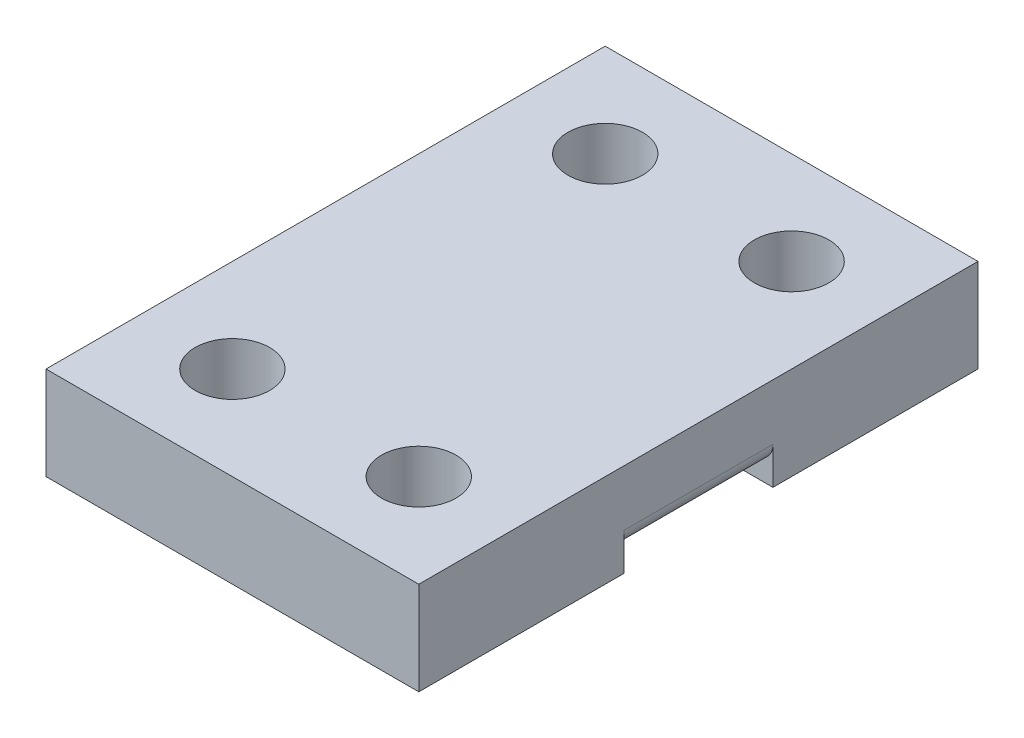
SolidWorks part; units mm, degrees
ref_plane "정면" through (0, 0, 0) normal (0, 0, 1) x (1, 0, 0)
ref_plane "윗면" through (0, 0, 0) normal (0, 1, 0) x (1, 0, 0)
ref_plane "우측면" through (0, 0, 0) normal (1, 0, 0) x (0, 0, -1)
sketch "스케치1" plane through (0, 0, 0) normal (0, 1, 0) x (1, 0, 0)
  line L0 (0, 0) -> (0, 30) construction
  line L1 (-10, 30) -> (10, 30)
  line L2 (10, 30) -> (10, 0)
  line L3 (-10, 30) -> (-10, 0)
  line L4 (10, 0) -> (-10, 0)
  line L5 (5, 25) -> (-5, 25) construction
  line L6 (5, 25) -> (5, 5) construction
  line L7 (-5, 25) -> (-5, 5) construction
  line L8 (5, 5) -> (-5, 5) construction
  circle A0 centre (5, 25) radius 2
  circle A1 centre (-5, 25) radius 2
  circle A2 centre (5, 5) radius 2
  circle A3 centre (-5, 5) radius 2
  point P16 (0, 25)
  point P17 (0, 5)
  dimension "D3" = 4
  dimension "D1" = 30
  dimension "D2" = 20
  dimension "D4" = 5
  dimension "D5" = 10
  dimension "D6" = 20
extrude "보스-돌출1" add sketch "스케치1" along normal blind 5
sketch "스케치3" plane through (0, 0, -30) normal (0, 0, -1) x (-1, 0, 0)
  line L0 (0, 0) -> (-1, 1)
  line L1 (-10, 0) -> (10, 0) construction
  line L2 (-1, 1) -> (-1, 0)
  line L3 (-1, 0) -> (0, 0)
  line L4 (0, 0) -> (1, 1)
  line L5 (1, 1) -> (1, 0)
  line L6 (1, 0) -> (0, 0)
  line L7 (1, 0) -> (2, 0)
  line L8 (2, 0) -> (1, 1)
  line L9 (1, 1) -> (1, 0)
  line L10 (2, 0) -> (3, 1)
  line L11 (3, 1) -> (3, 0)
  line L12 (3, 0) -> (2, 0)
  line L13 (3, 0) -> (4, 0)
  line L14 (4, 0) -> (3, 1)
  line L15 (3, 1) -> (3, 0)
  line L16 (4, 0) -> (5, 1)
  line L17 (5, 1) -> (5, 0)
  line L18 (5, 0) -> (4, 0)
  line L19 (5, 0) -> (6, 0)
  line L20 (6, 0) -> (5, 1)
  line L21 (5, 1) -> (5, 0)
  line L22 (6, 0) -> (7, 1)
  line L23 (7, 1) -> (7, 0)
  line L24 (7, 0) -> (6, 0)
  line L25 (7, 0) -> (8, 0)
  line L26 (8, 0) -> (7, 1)
  line L27 (7, 1) -> (7, 0)
  line L28 (8, 0) -> (9, 1)
  line L29 (9, 1) -> (9, 0)
  line L30 (9, 0) -> (8, 0)
  line L31 (9, 0) -> (10, 0)
  line L32 (10, 0) -> (9, 1)
  line L33 (9, 1) -> (9, 0)
  line L37 (0, 0) -> (0, 5) construction
  line L38 (-10, 5) -> (10, 5) construction
  line L39 (-9, 0) -> (-10, 0)
  line L40 (-10, 0) -> (-9, 1)
  line L41 (-9, 1) -> (-9, 0)
  line L42 (-9, 0) -> (-8, 0)
  line L43 (-9, 1) -> (-9, 0)
  line L44 (-8, 0) -> (-9, 1)
  line L45 (-7, 1) -> (-7, 0)
  line L46 (-8, 0) -> (-7, 1)
  line L47 (-7, 0) -> (-8, 0)
  line L48 (-7, 0) -> (-6, 0)
  line L49 (-7, 1) -> (-7, 0)
  line L50 (-6, 0) -> (-7, 1)
  line L51 (-5, 1) -> (-5, 0)
  line L52 (-6, 0) -> (-5, 1)
  line L53 (-5, 0) -> (-6, 0)
  line L54 (-5, 0) -> (-4, 0)
  line L55 (-5, 1) -> (-5, 0)
  line L56 (-4, 0) -> (-5, 1)
  line L57 (-3, 1) -> (-3, 0)
  line L58 (-4, 0) -> (-3, 1)
  line L59 (-3, 0) -> (-4, 0)
  line L60 (-3, 0) -> (-2, 0)
  line L61 (-3, 1) -> (-3, 0)
  line L62 (-2, 0) -> (-3, 1)
  line L63 (10, 0) -> (11, 1) [skipped]
  line L64 (11, 1) -> (11, 0) [skipped]
  line L65 (11, 0) -> (10, 0) [skipped]
  line L66 (-1, 1) -> (-2, 0)
  line L67 (-9, 1) -> (-10, 1)
  line L68 (-10, 5) -> (-10, 0) construction
  line L69 (-10, 1) -> (-10, 0)
  line L70 (9, 1) -> (10, 1)
  line L71 (10, 5) -> (10, 0) construction
  line L72 (10, 1) -> (10, 0)
  line M7 (-10, 0) -> (10, 0)
  line M8 (10, 0) -> (10, 5)
  line M10 (-10, 5) -> (-10, 0)
  dimension "D1" = 2
  dimension "D2" = 1
  dimension "D3" = 6
extrude "컷-돌출6" cut sketch "스케치3" against normal blind 4 and the other way blind 4 from offset 15 contours L41 L40 M7 | L44 L41 M7 | L46 L45 M7 | L50 L45 M7 | L52 L51 M7 | L56 L51 M7 | L58 L57 M7 | L62 L57 M7 | L2 L66 M7 | L0 L2 M7 | L5 L4 M7 | L8 L5 M7 | L11 L10 M7 | L14 L11 M7 | L20 L17 M7 | L23 L22 M7 | L26 L23 M7 | L29 L28 M7 | L32 L29 M7 | L40 L67 M10 | L70 L32 M8 | L16 L17 L18 region at (0.6667, 0.3333, -30) region at (8.6667, 0.3333, -30) region at (6.6667, 0.3333, -30) region at (4.6667, 0.3333, -30) region at (2.6667, 0.3333, -30) region at (-8.6667, 0.3333, -30) region at (-6.6667, 0.3333, -30) region at (-2.6667, 0.3333, -30) region at (-0.6667, 0.3333, -30) region at (1.3333, 0.3333, -30) region at (-1.3333, 0.3333, -30) region at (3.3333, 0.3333, -30) region at (-3.3333, 0.3333, -30) region at (5.3333, 0.3333, -30) region at (-5.3333, 0.3333, -30) region at (7.3333, 0.3333, -30) region at (-7.3333, 0.3333, -30) region at (9.3333, 0.3333, -30) region at (9.6667, 0.6667, -30) region at (-9.3333, 0.3333, -30) region at (-9.6667, 0.6667, -30) offset against normal yes
fillet "필렛1" radius 1 2 edges at (10, 1, -15) (-10, 1, -15)
